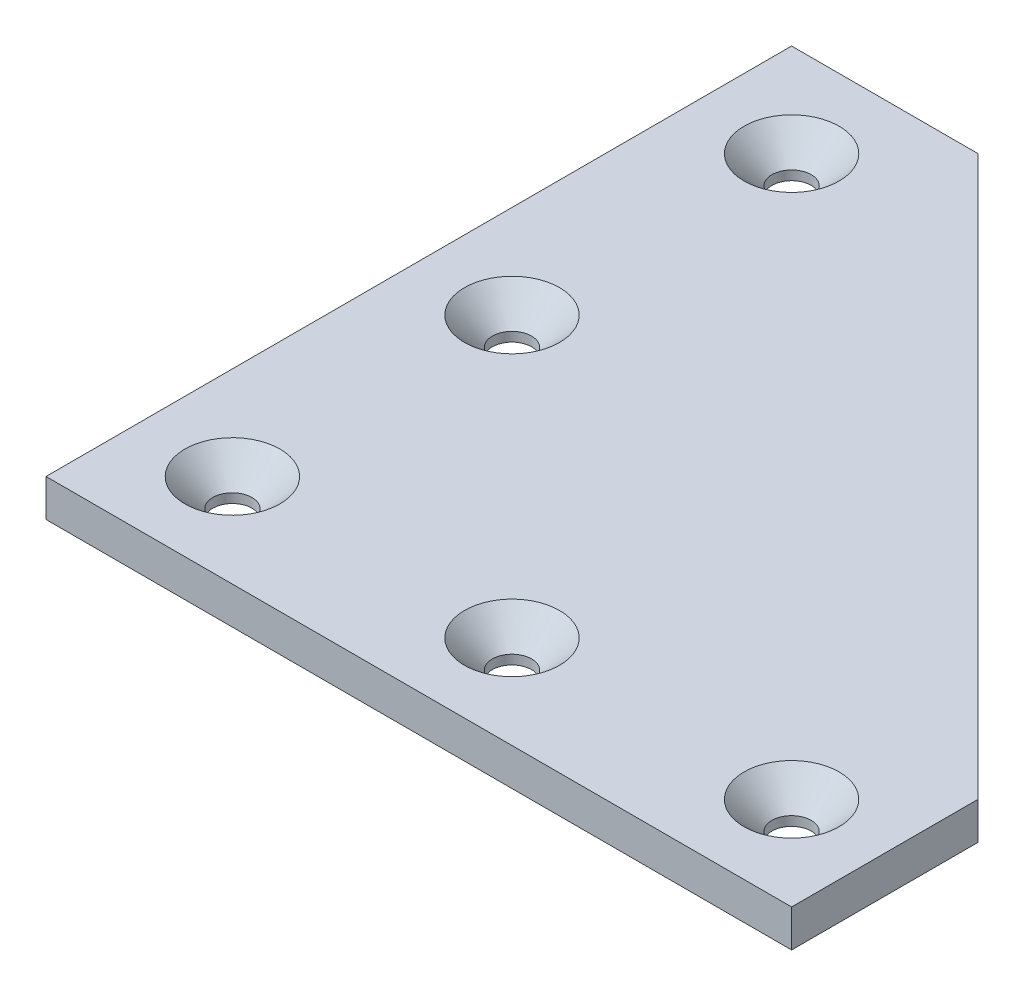
SolidWorks part; units mm, degrees
material "Aluminum 6105-T5"
ref_plane "Front Plane" through (0, 0, 0) normal (0, 0, 1) x (1, 0, 0)
ref_plane "Top Plane" through (0, 0, 0) normal (0, 1, 0) x (1, 0, 0)
ref_plane "Right Plane" through (0, 0, 0) normal (1, 0, 0) x (0, 0, -1)
sketch "Sketch1" plane through (0, 0, 0) normal (0, 1, 0) x (1, 0, 0)
  line L0 (0, 0) -> (0, 80)
  line L1 (0, 80) -> (20, 80)
  line L2 (20, 80) -> (80, 20)
  line L3 (80, 20) -> (80, 0)
  line L4 (80, 0) -> (0, 0)
  dimension "D1" = 20
  dimension "D2" = 20
  dimension "D3" = 45
  dimension "D4" = 80
extrude "Boss-Extrude1" add sketch "Sketch1" along normal blind 4
fillet "Fillet1" [suppressed] radius 1
sketch "Sketch3" plane through (0, 4, 0) normal (0, 1, 0) x (1, 0, 0)
  line L0 (0, 80) -> (0, 0) construction
  line L1 (0, 0) -> (80, 0) construction
  line L3 (80, 0) -> (80, 20) construction
  line L4 (20, 80) -> (0, 80) construction
  circle A2 centre (10, 10) radius 2.1
  circle A5 centre (40, 10) radius 2.1
  circle A6 centre (70, 10) radius 2.1
  circle A7 centre (10, 40) radius 2.1
  circle A8 centre (10, 70) radius 2.1
  dimension "D3" = 4.2
  dimension "D7" = 10
  dimension "D1" = 10
  dimension "D2" = 10
  dimension "D4" = 3
  dimension "D6" = 10
  dimension "D5" = 3
extrude "Cut-Extrude1" cut sketch "Sketch3" against normal blind 4
chamfer "Chamfer1" distance 3 angle 45 5 edges at (70, 4, -7.9) (40, 4, -7.9) (10, 4, -7.9) (10, 4, -37.9) (10, 4, -67.9)
